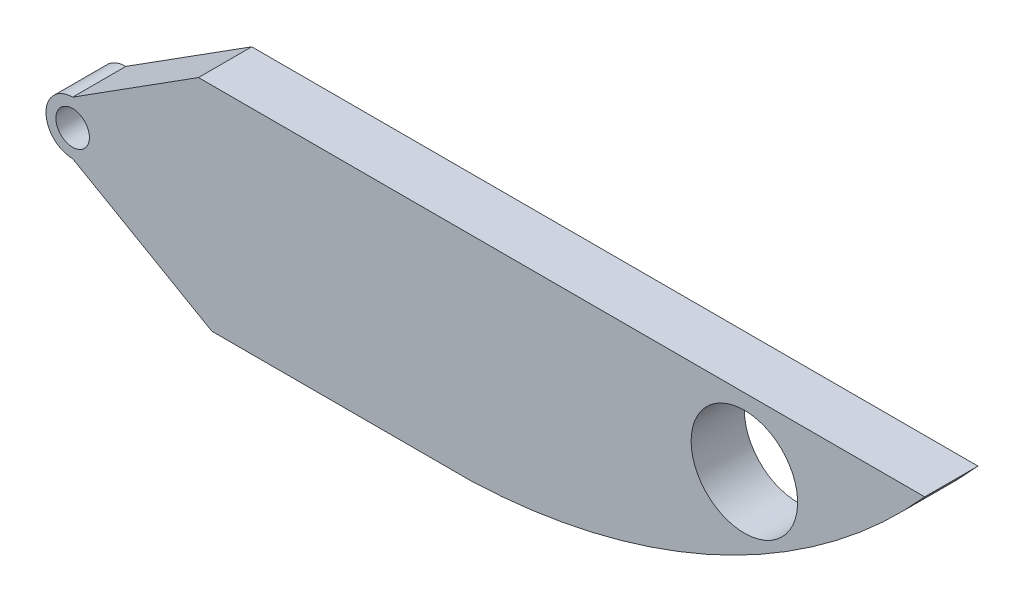
SolidWorks part; units mm, degrees
ref_plane "Front Plane" through (0, 0, 0) normal (0, 0, 1) x (1, 0, 0)
ref_plane "Top Plane" through (0, 0, 0) normal (0, 1, 0) x (1, 0, 0)
ref_plane "Right Plane" through (0, 0, 0) normal (1, 0, 0) x (0, 0, -1)
sketch "Sketch1" plane through (0, 0, 0) normal (0, 0, 1) x (1, 0, 0)
  line L1 (107.95, 25.4) -> (-107.95, 25.4)
  line L2 (107.95, 25.4) -> (107.95, -25.4)
  line L3 (107.95, -25.4) -> (-107.95, -25.4)
  line L4 (-107.95, 25.4) -> (-107.95, -25.4)
  line L5 (107.95, 25.4) -> (-107.95, -25.4) construction
  line L6 (107.95, -25.4) -> (-107.95, 25.4) construction
  point P0 (0, 0)
  dimension "D1" = 215.9
  dimension "D2" = 50.8
extrude "Boss-Extrude1" add sketch "Sketch1" along normal blind 12.7
sketch "Sketch3" plane through (0, 0, 12.7) normal (0, 0, 1) x (1, 0, 0)
  line L0 (0, 0) -> (-107.95, 0) construction
  line L1 (-107.95, 25.4) -> (-107.95, -25.4) construction
  circle A0 centre (-95.25, 0) radius 4
  dimension "D2" = 8
  dimension "D1" = 12.7
extrude "Cut-Extrude1" cut sketch "Sketch3" against normal through all
sketch "Sketch5" plane through (0, 0, 12.7) normal (0, 0, 1) x (1, 0, 0)
  line L0 (-107.95, -25.4) -> (107.95, -25.4) construction
  line L1 (-95.25, -6.35) -> (-62.0461, -25.4)
  line L2 (-95.25, 6.35) -> (-65.2393, 25.4)
  line L3 (107.95, 25.4) -> (-107.95, 25.4) construction
  line L4 (-65.2393, 25.4) -> (-107.95, 25.4)
  line L5 (-107.95, 25.4) -> (-107.95, -25.4)
  line L6 (-107.95, -25.4) -> (-62.0461, -25.4)
  line L7 (107.95, 25.4) -> (107.95, -25.4)
  line L8 (107.95, -25.4) -> (0, -25.4)
  arc A0 (0, -25.4) -> (107.95, 25.4) centre (-5.7388, 126.8919) ccw
  arc A2 (-95.25, 6.35) -> (-95.25, -6.35) centre (-95.25, 0) ccw
  line M3 (-107.95, 25.4) -> (-107.95, -25.4)
  line M4 (-107.95, -25.4) -> (107.95, -25.4)
  line M5 (107.95, -25.4) -> (107.95, 25.4)
  line M6 (107.95, 25.4) -> (-107.95, 25.4)
  dimension "D1" = 152.4
  dimension "D2" = 12.7
extrude "Cut-Extrude2" cut sketch "Sketch5" against normal through all contours A0 L8 M5 | A2 L2 L1 M6 M3 M4 region at (-78.9888, -16.4689, 12.7) region at (80.7498, -10.7022, 12.7)
sketch "Sketch6" plane through (0, 0, 12.7) normal (0, 0, 1) x (1, 0, 0)
  line L0 (-95.25, 0) -> (78.6662, 0) construction
  arc A0 (0, -25.4) -> (107.95, 25.4) centre (-5.7388, 126.8919) ccw construction
  circle A1 centre (31.75, 0) radius 3.1347
  dimension "D1" = 127
sketch "Sketch7" plane through (0, 0, 0) normal (0, 0, -1) x (-1, 0, 0)
  line L0 (44.0204, -2.9977) -> (44.0204, 16.0523) construction
  point P3 (44.0204, -2.9977)
  point P4 (44.0204, 16.0523)
  dimension "D1" = 19.05
sketch "Sketch11" plane through (0, 0, 0) normal (0, 0, -1) x (-1, 0, 0)
  circle A1 centre (-64.9363, 9.0871) radius 12.7
  point P2 (-81.2326, 5.9618)
  point P3 (-64.9363, 9.0871)
  dimension "D1" = 25.4
extrude "Cut-Extrude3" cut sketch "Sketch11" against normal through all
